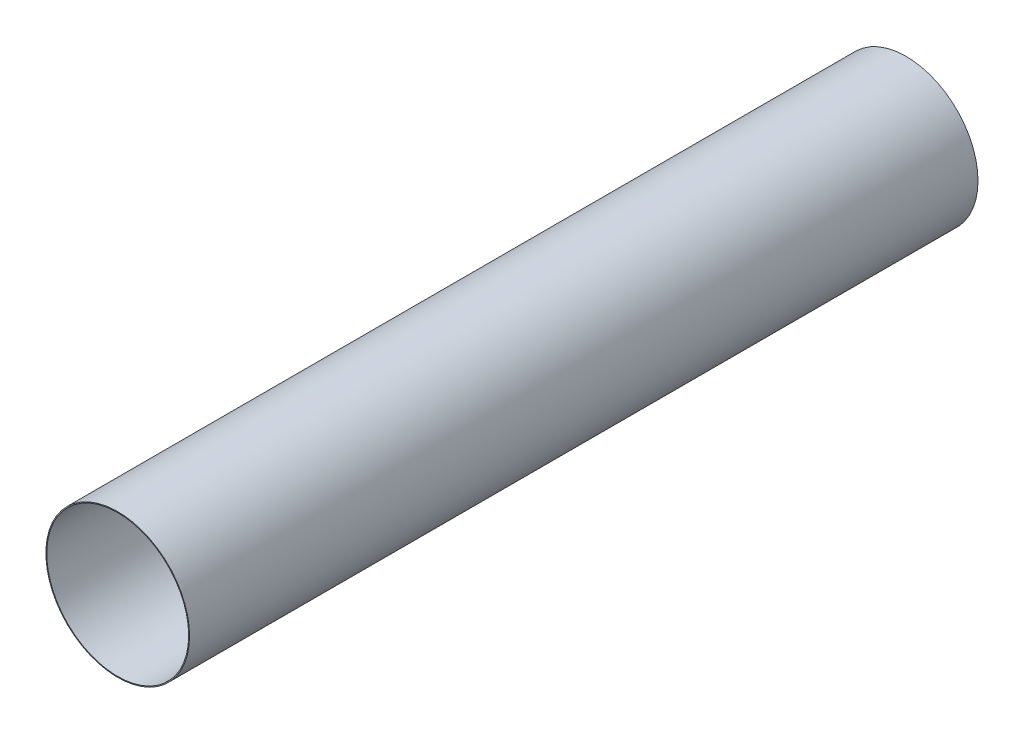
SolidWorks part; units mm, degrees
ref_plane "Front Plane" through (0, 0, 0) normal (0, 0, 1) x (1, 0, 0)
ref_plane "Top Plane" through (0, 0, 0) normal (0, 1, 0) x (1, 0, 0)
ref_plane "Right Plane" through (0, 0, 0) normal (1, 0, 0) x (0, 0, -1)
sketch "Sketch1" plane through (0, 0, 0) normal (0, 0, 1) x (1, 0, 0)
  circle A0 centre (0, 0) radius 82
  circle A1 centre (0, 0) radius 81
  dimension "D1" = 162
  dimension "D2" = 164
extrude "Boss-Extrude1" add sketch "Sketch1" along normal mid plane 900
